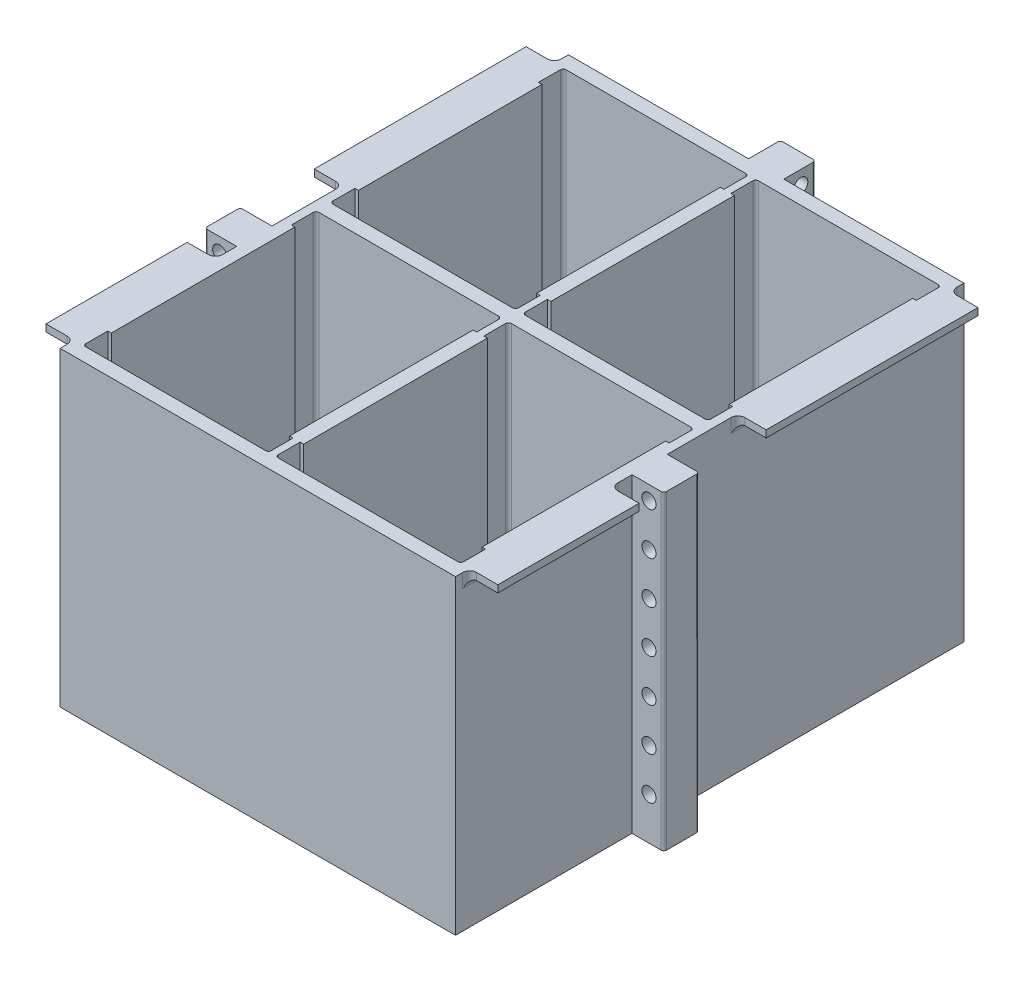
SolidWorks part; units mm, degrees
material "6061 Alloy"
ref_plane "Front Plane" through (0, 0, 0) normal (0, 0, 1) x (1, 0, 0)
ref_plane "Top Plane" through (0, 0, 0) normal (0, 1, 0) x (1, 0, 0)
ref_plane "Right Plane" through (0, 0, 0) normal (1, 0, 0) x (0, 0, -1)
sketch "Sketch1" plane through (0, 0, 0) normal (0, 1, 0) x (1, 0, 0)
  line L0 (-31.75, -228.6) -> (31.75, -228.6) construction
  line L1 (177.8, 228.6) -> (-177.8, 228.6) construction
  line L2 (177.8, 228.6) -> (177.8, -228.6) construction
  line L3 (177.8, -228.6) -> (-177.8, -228.6) construction
  line L4 (-177.8, 228.6) -> (-177.8, -228.6) construction
  line L5 (177.8, 228.6) -> (-177.8, -228.6) construction
  line L6 (177.8, -228.6) -> (-177.8, 228.6) construction
  line L7 (-31.75, -228.6) -> (-31.75, -269.875) construction
  line L8 (31.75, -228.6) -> (31.75, -269.875) construction
  line L9 (-31.75, -269.875) -> (31.75, -269.875) construction
  line L10 (-177.8, -228.6) -> (-31.75, -228.6)
  line L11 (31.75, -228.6) -> (-31.75, -228.6)
  line L12 (15.875, 228.6) -> (-15.875, 228.6) construction
  line L13 (15.875, 228.6) -> (15.875, 257.175)
  line L14 (31.75, -228.6) -> (177.8, -228.6)
  line L15 (-15.875, 228.6) -> (-15.875, 257.175)
  line L16 (15.875, 257.175) -> (-15.875, 257.175)
  line L17 (-15.875, 228.6) -> (-177.8, 228.6)
  line L18 (15.875, 228.6) -> (177.8, 228.6)
  line L19 (-177.8, -38.1) -> (-206.375, -38.1)
  line L20 (-177.8, -38.1) -> (-177.8, -69.85) construction
  line L21 (-206.375, -38.1) -> (-206.375, -69.85)
  line L22 (-177.8, -69.85) -> (-206.375, -69.85)
  line L23 (177.8, -38.1) -> (177.8, -69.85) construction
  line L24 (177.8, -38.1) -> (206.375, -38.1)
  line L25 (177.8, -69.85) -> (206.375, -69.85)
  line L26 (206.375, -38.1) -> (206.375, -69.85)
  line L27 (-177.8, 228.6) -> (-177.8, -38.1)
  line L28 (-177.8, -69.85) -> (-177.8, -228.6)
  line L29 (177.8, -69.85) -> (177.8, -228.6)
  line L30 (177.8, -38.1) -> (177.8, 228.6)
  point P0 (0, 0)
  point P6 (192.0875, -38.1)
  point P13 (0, 228.6)
  point P22 (192.0875, -69.85)
  point P25 (-192.0875, -69.85)
  dimension "D1" = 355.6
  dimension "D2" = 457.2
  dimension "D3" = 146.05
  dimension "D4" = 146.05
  dimension "D5" = 41.275
  dimension "D6" = 161.925
  dimension "D7" = 31.75
  dimension "D8" = 28.575
  dimension "D9" = 266.7
  dimension "D10" = 266.7
  dimension "D11" = 31.75
  dimension "D12" = 31.75
  dimension "D13" = 28.575
  dimension "D14" = 28.575
extrude "Boss-Extrude1" add sketch "Sketch1" along normal blind 279.4
ref_point "Point2"
ref_axis "Axis1" through (0, 139.7, 228.6) along (0, 1, 0)
sketch "Sketch2" plane through (0, 0, 69.85) normal (0, 0, 1) x (1, 0, 0)
  line L0 (-193.04, 279.4) -> (-193.04, 0) construction
  line L1 (-206.375, 279.4) -> (-177.8, 279.4) construction
  line L2 (-206.375, 0) -> (-177.8, 0) construction
  line L3 (-177.8, 279.4) -> (-177.8, 0) construction
  line L4 (0, 135.6782) -> (0, 345.0284)
  line L5 (0, 139.7) -> (0, 350.0578) construction
  line L6 (193.04, 279.4) -> (193.04, 0) construction
  circle A0 centre (-193.04, 38.1) radius 6.35
  circle A1 centre (-193.04, 76.2) radius 6.35
  circle A2 centre (-193.04, 114.3) radius 6.35
  circle A3 centre (-193.04, 152.4) radius 6.35
  circle A4 centre (-193.04, 190.5) radius 6.35
  circle A5 centre (-193.04, 228.6) radius 6.35
  circle A6 centre (-193.04, 266.7) radius 6.35
  circle A7 centre (193.04, 266.7) radius 6.35
  circle A8 centre (193.04, 228.6) radius 6.35
  circle A9 centre (193.04, 190.5) radius 6.35
  circle A10 centre (193.04, 152.4) radius 6.35
  circle A11 centre (193.04, 114.3) radius 6.35
  circle A12 centre (193.04, 76.2) radius 6.35
  circle A13 centre (193.04, 38.1) radius 6.35
  point P10 (-193.04, 53.7554)
  point P45 (193.04, 53.7554)
  dimension "D2" = 12.7
  dimension "D1" = 15.24
  dimension "D3" = 38.1
  dimension "D4" = 7
extrude "Cut-Extrude1" cut sketch "Sketch2" against normal blind 45.72 contours A6 | A5 | A3 | A4 | A2 | A1 | A0 | A7 | A8 | A9 | A10 | A11 | A12 | A13
sketch "Sketch3" plane through (-15.875, 0, 0) normal (-1, 0, 0) x (0, 0, 1)
  line L0 (-243.84, 279.4) -> (-243.84, 0) construction
  line L1 (-257.175, 279.4) -> (-228.6, 279.4) construction
  line L2 (-257.175, 0) -> (-228.6, 0) construction
  line L3 (-228.6, 279.4) -> (-228.6, 0) construction
  circle A0 centre (-243.84, 38.1) radius 6.35
  circle A1 centre (-243.84, 76.2) radius 6.35
  circle A2 centre (-243.84, 114.3) radius 6.35
  circle A3 centre (-243.84, 152.4) radius 6.35
  circle A4 centre (-243.84, 190.5) radius 6.35
  circle A5 centre (-243.84, 228.6) radius 6.35
  circle A6 centre (-243.84, 266.7) radius 6.35
  point P10 (-243.84, 53.0999)
  dimension "D2" = 12.7
  dimension "D1" = 15.24
  dimension "D3" = 38.1
  dimension "D4" = 7
extrude "Cut-Extrude2" cut sketch "Sketch3" against normal blind 45.72
fillet "Fillet1" radius 2.54 6 edges at (206.375, 139.7, 69.85) (206.375, 139.7, 38.1) (15.875, 139.7, -257.175) (-15.875, 139.7, -257.175) (-206.375, 139.7, 69.85) (-206.375, 139.7, 38.1)
sketch "Sketch4" plane through (0, 279.4, 0) normal (0, 1, 0) x (1, 0, 0)
  line L0 (177.8, 215.9) -> (-177.8, 215.9) construction
  line L1 (177.8, -228.6) -> (-177.8, -228.6) construction
  line L2 (177.8, -228.6) -> (177.8, 228.6) construction
  line L3 (177.8, 228.6) -> (-177.8, 228.6) construction
  line L4 (-177.8, -228.6) -> (-177.8, 228.6) construction
  line L5 (177.8, -228.6) -> (-177.8, 228.6) construction
  line L6 (177.8, 228.6) -> (-177.8, -228.6) construction
  line L7 (0, 0) -> (-177.8, 0) construction
  line L8 (0, 0) -> (0, 215.9) construction
  line L9 (-177.8, -6.35) -> (177.8, -6.35) construction
  line L10 (-177.8, -6.35) -> (-177.8, 6.35) construction
  line L11 (-177.8, 6.35) -> (177.8, 6.35) construction
  line L12 (177.8, -6.35) -> (177.8, 6.35) construction
  line L13 (-177.8, -6.35) -> (177.8, 6.35) construction
  line L14 (-177.8, 6.35) -> (177.8, -6.35) construction
  line L15 (-3.175, 215.9) -> (-3.175, 6.35) construction
  line L16 (-169.8625, 215.9) -> (-169.8625, 6.35) construction
  line L17 (-169.8625, 215.9) -> (-3.175, 215.9) construction
  line L18 (-169.8625, 215.9) -> (-169.8625, 193.675) construction
  line L19 (-3.175, 215.9) -> (-3.175, 193.675) construction
  line L20 (-169.8625, 193.675) -> (-3.175, 193.675) construction
  line L21 (-3.175, 6.35) -> (-169.8625, 6.35) construction
  line L22 (-3.175, 6.35) -> (-3.175, 28.575) construction
  line L23 (-169.8625, 6.35) -> (-169.8625, 28.575) construction
  line L24 (-3.175, 28.575) -> (-169.8625, 28.575) construction
  line L25 (-6.35, 28.575) -> (-6.35, 193.675) construction
  line L26 (-166.6875, 28.575) -> (-166.6875, 193.675) construction
  line L27 (-3.175, 215.9) -> (-169.8625, 215.9)
  line L28 (-169.8625, 215.9) -> (-169.8625, 193.675)
  line L29 (-169.8625, 193.675) -> (-166.6875, 193.675)
  line L30 (-166.6875, 193.675) -> (-166.6875, 28.575)
  line L31 (-166.6875, 28.575) -> (-169.8625, 28.575)
  line L32 (-169.8625, 28.575) -> (-169.8625, 6.35)
  line L33 (-169.8625, 6.35) -> (-3.175, 6.35)
  line L34 (-3.175, 6.35) -> (-3.175, 28.575)
  line L35 (-3.175, 28.575) -> (-6.35, 28.575)
  line L36 (-6.35, 28.575) -> (-6.35, 193.675)
  line L37 (-6.35, 193.675) -> (-3.175, 193.675)
  line L38 (-3.175, 193.675) -> (-3.175, 215.9)
  line L39 (3.175, 28.575) -> (6.35, 28.575)
  line L40 (3.175, 6.35) -> (3.175, 28.575)
  line L41 (169.8625, 6.35) -> (3.175, 6.35)
  line L42 (169.8625, 28.575) -> (169.8625, 6.35)
  line L43 (166.6875, 28.575) -> (169.8625, 28.575)
  line L44 (166.6875, 193.675) -> (166.6875, 28.575)
  line L45 (169.8625, 193.675) -> (166.6875, 193.675)
  line L46 (6.35, 28.575) -> (6.35, 193.675)
  line L47 (6.35, 193.675) -> (3.175, 193.675)
  line L48 (169.8625, 215.9) -> (169.8625, 193.675)
  line L49 (3.175, 215.9) -> (169.8625, 215.9)
  line L50 (3.175, 193.675) -> (3.175, 215.9)
  line L51 (-166.6875, -28.575) -> (-166.6875, -193.675) construction
  line L52 (-6.35, -28.575) -> (-6.35, -193.675) construction
  line L53 (-3.175, -28.575) -> (-169.8625, -28.575) construction
  line L54 (-169.8625, -6.35) -> (-169.8625, -28.575) construction
  line L55 (-3.175, -6.35) -> (-3.175, -28.575) construction
  line L56 (-3.175, -6.35) -> (-169.8625, -6.35) construction
  line L57 (-169.8625, -193.675) -> (-3.175, -193.675) construction
  line L58 (-3.175, -215.9) -> (-3.175, -193.675) construction
  line L59 (-169.8625, -215.9) -> (-169.8625, -193.675) construction
  line L60 (-169.8625, -215.9) -> (-3.175, -215.9) construction
  line L61 (-169.8625, -215.9) -> (-169.8625, -6.35) construction
  line L62 (-3.175, -215.9) -> (-3.175, -6.35) construction
  line L63 (-177.8, -6.35) -> (177.8, -6.35) construction
  line L64 (177.8, -215.9) -> (-177.8, -215.9) construction
  line L65 (3.175, -193.675) -> (3.175, -215.9)
  line L66 (3.175, -215.9) -> (169.8625, -215.9)
  line L67 (169.8625, -215.9) -> (169.8625, -193.675)
  line L68 (6.35, -193.675) -> (3.175, -193.675)
  line L69 (6.35, -28.575) -> (6.35, -193.675)
  line L70 (169.8625, -193.675) -> (166.6875, -193.675)
  line L71 (166.6875, -193.675) -> (166.6875, -28.575)
  line L72 (166.6875, -28.575) -> (169.8625, -28.575)
  line L73 (169.8625, -28.575) -> (169.8625, -6.35)
  line L74 (169.8625, -6.35) -> (3.175, -6.35)
  line L75 (3.175, -6.35) -> (3.175, -28.575)
  line L76 (3.175, -28.575) -> (6.35, -28.575)
  line L77 (-3.175, -193.675) -> (-3.175, -215.9)
  line L78 (-6.35, -193.675) -> (-3.175, -193.675)
  line L79 (-6.35, -28.575) -> (-6.35, -193.675)
  line L80 (-3.175, -28.575) -> (-6.35, -28.575)
  line L81 (-3.175, -6.35) -> (-3.175, -28.575)
  line L82 (-169.8625, -6.35) -> (-3.175, -6.35)
  line L83 (-169.8625, -28.575) -> (-169.8625, -6.35)
  line L84 (-166.6875, -28.575) -> (-169.8625, -28.575)
  line L85 (-166.6875, -193.675) -> (-166.6875, -28.575)
  line L86 (-169.8625, -193.675) -> (-166.6875, -193.675)
  line L87 (-169.8625, -215.9) -> (-169.8625, -193.675)
  line L88 (-3.175, -215.9) -> (-169.8625, -215.9)
  point P0 (0, 0)
  point P29 (-4.7625, 28.575)
  point P30 (4.7625, 28.575)
  point P68 (4.7625, -28.575)
  dimension "D1" = 12.7
  dimension "D2" = 12.7
  dimension "D3" = 3.175
  dimension "D4" = 7.9375
  dimension "D5" = 22.225
  dimension "D6" = 22.225
  dimension "D7" = 3.175
  dimension "D8" = 3.175
extrude "Cut-Extrude3" cut sketch "Sketch4" against normal blind 274.32
fillet "Fillet2" radius 2.54 16 edges at (169.8625, 142.24, 215.9) (-3.175, 142.24, 215.9) (-169.8625, 142.24, 215.9) (3.175, 142.24, 215.9) (169.8625, 142.24, 6.35) (-3.175, 142.24, 6.35) (-169.8625, 142.24, 6.35) (3.175, 142.24, 6.35) (-3.175, 142.24, -6.35) (-169.8625, 142.24, -6.35) (-3.175, 142.24, -215.9) (-169.8625, 142.24, -215.9) (3.175, 142.24, -215.9) (169.8625, 142.24, -215.9) (169.8625, 142.24, -6.35) (3.175, 142.24, -6.35)
sketch "Sketch6" plane through (177.8, 0, 0) normal (1, 0, 0) x (0, 0, -1)
  line L0 (-215.9, 279.4) -> (-215.9, 273.05)
  line L1 (-215.9, 279.4) -> (-88.9, 279.4)
  line L2 (-215.9, 273.05) -> (-88.9, 273.05)
  line L3 (-88.9, 279.4) -> (-88.9, 273.05)
  line L4 (-228.6, 279.4) -> (-228.6, 0) construction
  dimension "D1" = 127
  dimension "D2" = 6.35
  dimension "D3" = 12.7
extrude "Boss-Extrude2" add sketch "Sketch6" along normal blind 25.4
mirror "Mirror1" about plane through (0, 0, 0) normal (1, 0, 0) of "Boss-Extrude2"
sketch "Sketch8" plane through (177.8, 0, 0) normal (1, 0, 0) x (0, 0, -1)
  line L0 (215.9, 279.4) -> (215.9, 273.05)
  line L1 (215.9, 279.4) -> (25.4, 279.4)
  line L2 (215.9, 273.05) -> (25.4, 273.05)
  line L3 (25.4, 279.4) -> (25.4, 273.05)
  line L5 (228.6, 279.4) -> (228.6, 0) construction
  point P7 (215.9, 276.225)
  dimension "D1" = 6.35
  dimension "D2" = 190.5
  dimension "D3" = 12.7
extrude "Boss-Extrude3" add sketch "Sketch8" along normal blind 25.4
mirror "Mirror2" about plane through (0, 0, 0) normal (1, 0, 0) of "Boss-Extrude3"
fillet "Fillet3" radius 6.35 12 edges at (-177.8, 276.225, 88.9) (-177.8, 273.05, 152.4) (-177.8, 276.225, 215.9) (-177.8, 276.225, -25.4) (-177.8, 273.05, -120.65) (-177.8, 276.225, -215.9) (177.8, 276.225, -215.9) (177.8, 273.05, -120.65) (177.8, 276.225, -25.4) (177.8, 276.225, 88.9) (177.8, 276.225, 215.9) (177.8, 273.05, 152.4)
